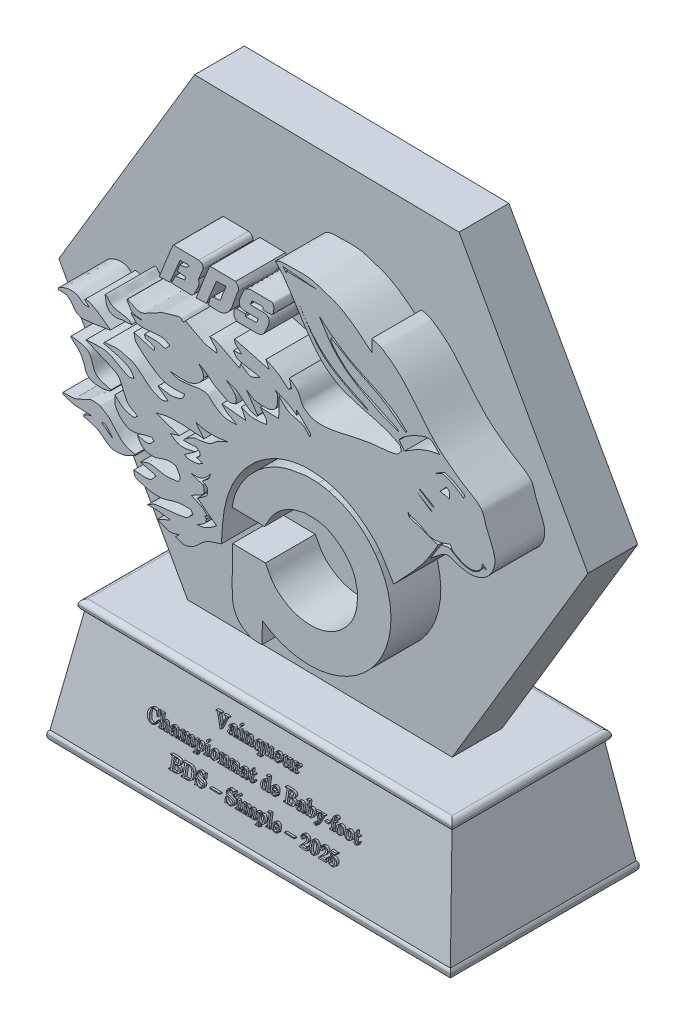
SolidWorks part; units mm, degrees
ref_plane "Plan de face" through (0, 0, 0) normal (0, 0, 1) x (1, 0, 0)
ref_plane "Plan de dessus" through (0, 0, 0) normal (0, 1, 0) x (1, 0, 0)
ref_plane "Plan de droite" through (0, 0, 0) normal (1, 0, 0) x (0, 0, -1)
sketch "Esquisse3" plane through (0, 0, 0) normal (0, 0, 1) x (1, 0, 0)
  line L0 (336.1667, 1024) -> (1680.8333, 1024) construction
  line L1 (1302, 1687) -> (1302, 1736)
  line L2 (1537, 1090) -> (1581, 1159)
  line L3 (1445.599, 1206.4377) -> (1452, 1191)
  line L4 (1452, 1191) -> (1568, 1151)
  line L5 (514, 653) -> (528, 667)
  line L6 (441, 677) -> (494, 701)
  line L7 (584, 764) -> (577, 778)
  line L8 (437, 826) -> (373, 842)
  line L9 (484, 1110) -> (443, 1141)
  line L10 (347, 1280) -> (428, 1256)
  line L11 (428, 1256) -> (430, 1269)
  line L12 (473, 1286) -> (491, 1306)
  line L13 (335, 1341) -> (376, 1337)
  line L14 (376, 1337) -> (378, 1339)
  line L15 (318, 1380) -> (321, 1382)
  line L16 (546, 1414) -> (554, 1424)
  line L17 (771, 1367) -> (775, 1384)
  line L18 (746, 1416) -> (780, 1420)
  line L19 (751, 1459) -> (890, 1422)
  line L20 (890, 1422) -> (877, 1451)
  line L21 (967, 1392) -> (980, 1399)
  line L22 (980, 1399) -> (971, 1433)
  line L23 (945, 1808) -> (1083, 1796)
  line L24 (1083, 1796) -> (959, 1800)
  line L25 (959, 1800) -> (958, 1794)
  line L26 (958, 1794) -> (960, 1791)
  line L27 (960, 1791) -> (945, 1808)
  line L28 (1444, 1481) -> (1437, 1478)
  line L29 (1433, 1410) -> (1411, 1437)
  line L30 (1677, 1373) -> (1670, 1365)
  line L31 (1613, 1334) -> (1576, 1342)
  line L32 (1601, 1369) -> (1576, 1342)
  line L33 (1000, 1318) -> (999, 1338)
  line L34 (999, 1338) -> (1057, 1281)
  line L35 (1057, 1281) -> (1053, 1269)
  line L36 (930, 1348) -> (928, 1270)
  line L37 (928, 1270) -> (855, 1273)
  line L38 (778, 1236) -> (797, 1198)
  line L39 (840, 1234) -> (844, 1240)
  line L40 (844, 1240) -> (799, 1306)
  line L41 (1654, 1326) -> (1658, 1324)
  line L42 (1658, 1324) -> (1654, 1325)
  line L43 (1654, 1326) -> (1654, 1325)
  line L44 (1551, 1277) -> (1494, 1309)
  line L45 (1551, 1277) -> (1549, 1272)
  line L46 (1549, 1272) -> (1493, 1307)
  line L47 (1493, 1307) -> (1494, 1309)
  line L48 (1483, 1293) -> (1544, 1256)
  line L49 (1542, 1254) -> (1544, 1256)
  line L50 (1542, 1254) -> (1483, 1293)
  line L51 (1746, 1175) -> (1763, 1163)
  line L52 (1763, 1163) -> (1760, 1162)
  line L53 (1760, 1162) -> (1750.0098, 1163.665)
  line L55 (1743, 1157) -> (1746, 1175)
  line L56 (598, 970) -> (623, 963)
  line L57 (550, 957) -> (594, 988)
  line L58 (493, 1001) -> (529, 1012)
  line L59 (529, 1012) -> (437, 1044)
  line L60 (595, 1092) -> (628, 1050)
  line L61 (602, 831) -> (679, 773)
  line L62 (638, 777) -> (631, 785)
  line L63 (631, 785) -> (643, 789)
  line L64 (574, 905) -> (625, 888)
  line L65 (232, 1354) -> (231, 1353)
  line L66 (168, 1277) -> (149, 1295)
  line L67 (153, 1299) -> (149, 1295)
  line L68 (255, 1034) -> (253, 1029)
  line L69 (95, 1141) -> (94, 1136)
  line L70 (352, 858) -> (352, 854)
  line L71 (144, 891) -> (144, 887)
  line L72 (144, 891) -> (174, 905)
  line L73 (62, 923) -> (62, 929)
  line L74 (1234, 1501) -> (1241.5869, 1497.8498)
  line L75 (678, 1623) -> (717, 1625)
  line L76 (862.8036, 535.7693) -> (861, 451)
  line L77 (743, 744) -> (875, 742)
  line L78 (871, 867) -> (741, 869)
  line L79 (865, 1617) -> (864, 1628)
  line L80 (821, 1627) -> (864, 1628)
  line L81 (821, 1627) -> (814, 1611)
  line L82 (794, 1568) -> (795, 1559)
  line L83 (795, 1559) -> (839, 1560)
  line L84 (839, 1560) -> (846, 1576)
  line L85 (693, 1564) -> (717, 1625)
  line L86 (700, 1208) -> (797, 1198)
  line L87 (678, 1623) -> (638, 1526)
  line L88 (638, 1526) -> (597, 1525)
  line L89 (498, 1527) -> (513, 1559)
  line L90 (513, 1559) -> (551, 1564)
  line L91 (551, 1564) -> (554, 1576)
  line L92 (554, 1576) -> (521, 1580)
  line L93 (521, 1580) -> (531, 1607)
  line L94 (567, 1620) -> (565, 1624)
  line L95 (565, 1624) -> (532, 1623)
  line L96 (532, 1623) -> (491, 1526)
  line L97 (491, 1526) -> (449, 1525)
  line L98 (624.8796, 1638.9367) -> (605.4226, 1592.9044)
  line L99 (604.6984, 1566.7534) -> (589.7477, 1536.2154)
  line L100 (573.9653, 1525) -> (498, 1527)
  line L101 (264.0246, 866.4916) -> (217, 902)
  arc A0 (607, 1661) -> (624.8796, 1638.9367) centre (606.6207, 1642.4164) cw
  arc A1 (605.4226, 1592.9044) -> (604.6984, 1566.7534) centre (576.3678, 1580.6235) cw
  arc A2 (589.7477, 1536.2154) -> (573.9653, 1525) centre (571.5353, 1545.1319) cw
  arc A3 (862.8036, 535.7693) -> (1316.5669, 993.1753) centre (1052.5129, 801.3486) ccw
  arc A4 (1129.8066, 1118.4411) -> (1086.8314, 1125.9164) centre (1052.5129, 801.3486) ccw
  spline S0 degree 3 poles (915, 1811) (920.6667, 1813.6667) (925.9164, 1817.5129) (932, 1819) (941.1183, 1821.2289) (950.6154, 1822.1997) (960, 1822) (1000.4122, 1821.1402) (1042.9169, 1827.5488) (1081, 1814) (1113.09, 1802.5833) (1146.9207, 1794.9796) (1177, 1779) (1222.6884, 1754.728) (1262.8151, 1720.7801) (1302, 1687) knots 0 0 0 0 1 1 1 2 2 2 3 3 3 4 4 4 5 5 5 5
  spline S1 degree 3 poles (1302, 1736) (1317, 1730.3333) (1333.5756, 1727.7691) (1347, 1719) (1375.3732, 1700.4659) (1402.4901, 1679.4098) (1426, 1655) (1472.4253, 1606.7976) (1509.2053, 1549.8439) (1556, 1502) (1583.8463, 1473.5293) (1617.0572, 1450.7835) (1649, 1427) (1678.4402, 1405.0798) (1714.1626, 1391.0701) (1740, 1365) (1752.6359, 1352.2503) (1753.5167, 1331.7388) (1760, 1315) (1771.8506, 1284.4039) (1788.3447, 1255.1289) (1795, 1223) (1798.2706, 1207.2107) (1795.1053, 1189.924) (1789, 1175) (1782.6895, 1159.5742) (1772.3333, 1145) (1759, 1135) (1744.6396, 1124.2297) (1726.7988, 1117.3288) (1709, 1115) (1690.0565, 1112.5214) (1670.8107, 1117.6598) (1652, 1121) (1635.0445, 1124.0108) (1618.6273, 1138.4821) (1602, 1134) (1576.7377, 1127.1902) (1558.6667, 1104.6667) (1537, 1090) knots 0 0 0 0 1 1 1 2 2 2 3 3 3 4 4 4 5 5 5 6 6 6 7 7 7 8 8 8 9 9 9 10 10 10 11 11 11 12 12 12 13 13 13 13
  spline S2 degree 3 poles (1581, 1159) (1592.9734, 1159.921) (1605.2835, 1164.5242) (1617, 1162.6354) knots 0 0 0 0 0.921032 0.921032 0.921032 0.921032
  spline S3 degree 3 poles (1626.6587, 1159.5467) (1622.8097, 1165.1023) (1620.6123, 1172.2204) (1617, 1178) knots 2.277549 2.277549 2.277549 2.277549 3 3 3 3
  spline S4 degree 3 poles (1617, 1178) (1603, 1173.6667) (1589.4463, 1167.4664) (1575, 1165) (1561.8527, 1162.7553) (1547.9107, 1160.6528) (1535, 1164) (1519.9865, 1167.8924) (1508.1253, 1179.5944) (1494, 1186) (1479.3968, 1192.6224) (1461.6455, 1193.1408) (1449, 1203) (1447.7012, 1204.0126) (1446.5813, 1205.1696) (1445.599, 1206.4377) knots 0 0 0 0 1 1 1 2 2 2 3 3 3 4 4 4 4.153424 4.153424 4.153424 4.153424
  spline S5 degree 3 poles (1568, 1151) (1562.6667, 1142) (1557.7044, 1132.7695) (1552, 1124) (1535.3644, 1098.4259) (1520.3192, 1071.6124) (1501, 1048) (1466.1847, 1005.448) (1427, 966.6667) (1390, 926) knots 0 0 0 0 1 1 1 2 2 2 3 3 3 3
  spline S6 degree 3 poles (1390, 926) (1370, 957.3333) (1353.6926, 991.3567) (1330, 1020) (1308.6483, 1045.8133) (1283.3166, 1068.6086) (1256, 1088) (1228.8829, 1107.2498) (1199.2278, 1123.5669) (1168, 1135) (1137.6118, 1146.1257) (1105.2971, 1152.9709) (1073, 1155) (1040.9523, 1157.0135) (1008.2798, 1154.2583) (977, 1147) (947.2739, 1140.1022) (918.485, 1128.1581) (892, 1113) (864.9769, 1097.534) (839.9344, 1078.0981) (818, 1056) (794.8916, 1032.7191) (774.5075, 1006.3461) (758, 978) (741.238, 949.2167) (728.0873, 918.0447) (719, 886) (703.7834, 832.3415) (700.9314, 775.6973) (698, 720) knots 0 0 0 0 1 1 1 2 2 2 3 3 3 4 4 4 5 5 5 6 6 6 7 7 7 8 8 8 9 9 9 10 10 10 10
  spline S7 degree 3 poles (698, 720) (678, 712.6667) (656.4567, 708.6361) (638, 698) (616.6203, 685.6795) (602.0285, 663.1191) (580, 652) (548.5317, 636.116) (537.3019, 642.1258) (514, 653) knots 0 0 0 0 1 1 1 2 2 2 3 3 3 3
  spline S8 degree 3 poles (528, 667) (525.4489, 666.4898) (497.27, 654.9179) (484, 660) (469.6066, 665.5124) (455.3333, 671.3333) (441, 677) knots 0 0 0 0 1 1 1 2 2 2 2
  spline S9 degree 3 poles (494, 701) (477, 703.3333) (460.1099, 706.6982) (443, 708) (429.3727, 709.0369) (415.6667, 708) (402, 708) knots 0 0 0 0 1 1 1 2 2 2 2
  spline S10 degree 3 poles (402, 708) (412, 713.3333) (420.9098, 721.6652) (432, 724) (472.1351, 732.4495) (514.3355, 729.562) (554, 740) (566.3846, 743.2591) (574, 756) (584, 764) knots 0 0 0 0 1 1 1 2 2 2 3 3 3 3
  spline S11 degree 3 poles (577, 778) (560, 777.6667) (542.804, 779.5957) (526, 777) (501.5513, 773.2234) (478.6767, 760.7501) (454, 759) (430.9039, 757.362) (407.166, 760.3084) (385, 767) (348.0895, 778.1428) (350.2029, 779.9856) (346, 801) knots 0 0 0 0 1 1 1 2 2 2 3 3 3 4 4 4 4
  spline S12 degree 3 poles (346, 801) (367.6667, 801) (390.1074, 795.2603) (411, 801) (422.5936, 804.185) (428.3333, 817.6667) (437, 826) knots 0 0 0 0 1 1 1 2 2 2 2
  spline S13 degree 3 poles (373, 842) (385, 846.3333) (396.25, 854.5364) (409, 855) (435.1955, 855.9526) (460.8999, 842.5721) (487, 845) (500.0501, 846.214) (513, 848.3333) (526, 850) knots 0 0 0 0 1 1 1 2 2 2 3 3 3 3
  spline S14 degree 3 poles (526, 850) (528, 856.3333) (533.3025, 862.4874) (532, 869) (529.7195, 880.4027) (521.3333, 889.6667) (516, 900) knots 0 0 0 0 1 1 1 2 2 2 2
  spline S15 degree 3 poles (516, 900) (505.3333, 901) (494.6103, 904.4832) (484, 903) (463.1813, 900.0899) (443.9834, 888.259) (423, 887) (409.6035, 886.1962) (395.1111, 889.4731) (384, 897) (373.1244, 904.3673) (368.6667, 918.3333) (361, 929) knots 0 0 0 0 1 1 1 2 2 2 3 3 3 4 4 4 4
  spline S16 degree 3 poles (361, 929) (376, 927) (391.1443, 920.1176) (406, 923) (415.5122, 924.8457) (420.6667, 935.6667) (428, 942) knots 0 0 0 0 1 1 1 2 2 2 2
  spline S17 degree 3 poles (428, 942) (424, 944.6667) (420.7819, 950.4947) (416, 950) (390.5019, 947.3623) (366.6332, 933.2229) (341, 933) (326.6401, 932.8751) (312.2458, 940.0695) (301, 949) (288.6786, 958.7846) (279.0102, 972.4593) (273, 987) (268.2733, 998.4355) (271, 1011.6667) (270, 1024) knots 0 0 0 0 1 1 1 2 2 2 3 3 3 4 4 4 5 5 5 5
  spline S18 degree 3 poles (270, 1024) (283.6667, 1013.6667) (294.8981, 998.8552) (311, 993) (347.6119, 979.6866) (348.3963, 982.3963) (362, 996) knots 0 0 0 0 1 1 1 2 2 2 2
  spline S19 degree 3 poles (362, 996) (349.3333, 1004) (334.0691, 1008.9069) (324, 1020) (313.6798, 1031.3697) (310.3408, 1047.5133) (303, 1061) (296.0028, 1073.8554) (292.6952, 1090.1997) (281, 1099) (257.6507, 1116.5698) (228.5806, 1124.8608) (202, 1137) (186.2331, 1144.2006) (170, 1150.3333) (154, 1157) knots 0 0 0 0 1 1 1 2 2 2 3 3 3 4 4 4 5 5 5 5
  spline S20 degree 3 poles (154, 1157) (155.3333, 1157.3333) (156.6257, 1157.9838) (158, 1158) (184.9981, 1158.3176) (212.8154, 1164.5853) (239, 1158) (269.9392, 1150.2189) (294.8755, 1126.5021) (325, 1116) (332.348, 1113.4383) (340.3333, 1118.6667) (348, 1120) knots 0 0 0 0 1 1 1 2 2 2 3 3 3 4 4 4 4
  spline S21 degree 3 poles (348, 1120) (341.6667, 1128.6667) (337.8909, 1139.9855) (329, 1146) (298.4419, 1166.6716) (259.637, 1171.4544) (224, 1181) knots 0 0 0 0 1 1 1 2 2 2 2
  spline S22 degree 3 poles (224, 1181) (226, 1182.6667) (227.4051, 1185.7896) (230, 1186) (253.9215, 1187.9396) (279.1881, 1193.4577) (302, 1186) (318.0306, 1180.7592) (335.4753, 1178.5719) (350, 1170) (376.6403, 1154.2779) (396.4202, 1128.0088) (424, 1114) (459.6438, 1095.8952) (463.5958, 1099.7979) (484, 1110) knots 0 0 0 0 1 1 1 2 2 2 3 3 3 4 4 4 5 5 5 5
  spline S23 degree 3 poles (443, 1141) (448.6949, 1142.8983) (443.1637, 1141.6511) (450, 1141) (469.6483, 1139.1287) (489.5876, 1132.4345) (509, 1136) (542.4065, 1142.1359) (543.3635, 1148.1815) (551, 1166) knots 0 0 0 0 1 1 1 2 2 2 3 3 3 3
  spline S24 degree 3 poles (551, 1166) (526.3333, 1166.3333) (501.1599, 1162.0146) (477, 1167) (458.1643, 1170.8867) (440.8598, 1181.1209) (425, 1192) (400.2227, 1208.996) (375.9299, 1227.515) (356, 1250) (349.0749, 1257.813) (350, 1270) (347, 1280) knots 0 0 0 0 1 1 1 2 2 2 3 3 3 4 4 4 4
  spline S25 degree 3 poles (430, 1269) (388.8184, 1289.0628) (394.9727, 1274.0957) (389, 1295) knots 0 0 0 0 1 1 1 1
  spline S26 degree 3 poles (389, 1295) (407, 1294.6667) (425.0994, 1295.9179) (443, 1294) (453.2906, 1292.8974) (463, 1288.6667) (473, 1286) knots 0 0 0 0 1 1 1 2 2 2 2
  spline S27 degree 3 poles (491, 1306) (482, 1310.3333) (473.9581, 1318.2159) (464, 1319) (430.7546, 1321.6178) (396.8737, 1310.3936) (364, 1316) (351.4189, 1318.1456) (344.6667, 1332.6667) (335, 1341) knots 0 0 0 0 1 1 1 2 2 2 3 3 3 3
  spline S28 degree 3 poles (378, 1339) (365.6667, 1341.6667) (351.4183, 1339.8809) (341, 1347) (329.9297, 1354.5647) (325.6667, 1369) (318, 1380) knots 0 0 0 0 1 1 1 2 2 2 2
  spline S29 degree 3 poles (321, 1382) (337.6667, 1375.6667) (353.1715, 1362.8181) (371, 1363) (388.3324, 1363.1769) (403.2308, 1375.8044) (419, 1383) (437.5803, 1391.4784) (454.2051, 1404.9727) (474, 1410) (535.009, 1425.4944) (528.4316, 1431.5684) (546, 1414) knots 0 0 0 0 1 1 1 2 2 2 3 3 3 4 4 4 4
  spline S30 degree 3 poles (554, 1424) (579.3333, 1410.6667) (603.3907, 1394.5593) (630, 1384) (645.7983, 1377.7308) (663.3333, 1377.3333) (680, 1374) knots 0 0 0 0 1 1 1 2 2 2 2
  spline S31 degree 3 poles (680, 1374) (679.3333, 1378) (680.2674, 1382.638) (678, 1386) (670.338, 1397.3609) (660, 1406.6667) (651, 1417) knots 0 0 0 0 1 1 1 2 2 2 2
  spline S32 degree 3 poles (651, 1417) (660, 1416) (669.6412, 1417.4828) (678, 1414) (710.0621, 1400.6408) (740, 1382.6667) (771, 1367) knots 0 0 0 0 1 1 1 2 2 2 2
  spline S33 degree 3 poles (775, 1384) (791.3079, 1376.2006) (808.3586, 1355.94) (825, 1363) (834.7522, 1367.1373) (844.3333, 1371.6667) (854, 1376) knots 0 0 0 0 1 1 1 2 2 2 2
  spline S34 degree 3 poles (854, 1376) (846, 1378) (838.054, 1380.2299) (830, 1382) (807.7162, 1386.8975) (784.1489, 1387.4397) (763, 1396) (754.8896, 1399.2828) (751.6667, 1409.3333) (746, 1416) knots 0 0 0 0 1 1 1 2 2 2 3 3 3 3
  spline S35 degree 3 poles (780, 1420) (749.6731, 1451.41) (753.337, 1435.6296) (751, 1459) knots 0 0 0 0 1 1 1 1
  spline S36 degree 3 poles (877, 1451) (893.6667, 1442.3333) (911.2896, 1435.2991) (927, 1425) (941.4558, 1415.5234) (953.6667, 1403) (967, 1392) knots 0 0 0 0 1 1 1 2 2 2 2
  spline S37 degree 3 poles (971, 1433) (982, 1424) (995.2325, 1417.1862) (1004, 1406) (1014.9466, 1392.0336) (1015.9477, 1371.0219) (1029, 1359) (1042.717, 1346.3659) (1061.5274, 1338.5577) (1080, 1336) (1108.8188, 1332.0097) (1138.5521, 1336.904) (1167, 1343) (1206.3139, 1351.4244) (1245.3733, 1361.1971) (1285, 1368) (1323.1007, 1374.5409) (1362.6291, 1373.1077) (1400, 1383) (1409.5699, 1385.5332) (1414, 1397) (1421, 1404) knots 0 0 0 0 1 1 1 2 2 2 3 3 3 4 4 4 5 5 5 6 6 6 7 7 7 7
  spline S38 degree 3 poles (1421, 1404) (1418.3333, 1410) (1418.5514, 1418.4939) (1413, 1422) (1392.0534, 1435.2294) (1368.4815, 1444.1007) (1345, 1452) (1296.0045, 1468.4823) (1244.0544, 1475.9476) (1196, 1495) (1167.7816, 1506.1879) (1141.5168, 1522.8061) (1118, 1542) (1095.6955, 1560.2044) (1076.9818, 1582.7512) (1060, 1606) (1020.8468, 1659.6027) (988.3318, 1717.8068) (950, 1772) (939.9132, 1786.2607) (926.6667, 1798) (915, 1811) knots 0 0 0 0 1 1 1 2 2 2 3 3 3 4 4 4 5 5 5 6 6 6 7 7 7 7
  spline S39 degree 3 poles (1234, 1501) (1233.3071, 1501.2746) (1232.6555, 1501.6452) (1232, 1502) (1204.3218, 1516.9788) (1175.736, 1530.3978) (1149, 1547) (1118.5402, 1565.9145) (1091.9951, 1591.6844) (1070, 1620) (1033.5835, 1666.8811) (1004.352, 1718.9828) (974, 1770) knots 5 5 5 5 6 6 6 7 7 7 8 8 8 9 9 9 9
  spline S40 degree 3 poles (974, 1770) (1009.2632, 1712.8836) (1040.7926, 1651.7205) (1088, 1604) (1103.129, 1588.7065) (1119.6469, 1574.7141) (1137, 1562) (1153.4175, 1549.9713) (1171.1465, 1539.7712) (1189, 1530) (1220.5161, 1512.7513) (1254.8005, 1500.4619) (1285, 1481) (1298.4541, 1472.3296) (1262.1817, 1489.0571) (1241.5869, 1497.8498) knots 0 0 0 0 1 1 1 2 2 2 3 3 3 4 4 4 4.876532 4.876532 4.876532 4.876532
  spline S41 degree 3 poles (1091, 1708) (1133.0564, 1673.7942) (1174.7177, 1637.6494) (1223, 1613) (1284.8912, 1581.4029) (1352.3155, 1557.8776) (1407, 1515) (1420.1811, 1504.6649) (1431.6667, 1492.3333) (1444, 1481) knots 0 0 0 0 1 1 1 2 2 2 3 3 3 3
  spline S42 degree 3 poles (1437, 1478) (1402.4117, 1505.2291) (1367.5024, 1532.6613) (1329, 1554) (1294.7083, 1573.005) (1258.5431, 1588.4558) (1224, 1607) (1195.1856, 1622.4688) (1167.3333, 1639.6667) (1139, 1656) knots 0 0 0 0 1 1 1 2 2 2 3 3 3 3
  spline S43 degree 3 poles (1139, 1656) (1139.3333, 1650.6667) (1136.7754, 1644.2611) (1140, 1640) (1156.078, 1618.7541) (1175.1654, 1599.7898) (1195, 1582) (1207.6652, 1570.6405) (1221.9981, 1561.0243) (1237, 1553) (1279.4612, 1530.2882) (1323.6737, 1511.0145) (1367, 1490) (1406.2609, 1470.9573) (1395.2349, 1482.5182) (1409, 1466) knots 0 0 0 0 1 1 1 2 2 2 3 3 3 4 4 4 5 5 5 5
  spline S44 degree 3 poles (1409, 1466) (1382.5166, 1475.5954) (1354.8689, 1482.7719) (1330, 1496) (1264.0429, 1531.0836) (1201.8033, 1560.9883) (1152, 1618) (1128.157, 1645.2939) (1110.3276, 1677.3424) (1091, 1708) knots 0 0 0 0 1 1 1 2 2 2 3 3 3 3
  spline S45 degree 3 poles (1411, 1437) (1422.7965, 1460.5929) (1479.2149, 1489.3274) (1503, 1497) (1509.6241, 1499.1368) (1516.0477, 1502.6689) (1523, 1503) (1528.3377, 1503.2542) (1533.6929, 1502.6244) (1539, 1502) (1546.2224, 1501.1503) (1568.8037, 1474.1963) (1574, 1469) knots 0 0 0 0 1 1 1 2 2 2 3 3 3 4 4 4 4
  spline S46 degree 3 poles (1574, 1469) (1515.6013, 1461.3828) (1480.7028, 1441.8019) (1433, 1410) knots 0 0 0 0 1 1 1 1
  spline S47 degree 3 poles (1556, 1394) (1558.3701, 1396.3701) (1590.3583, 1416) (1594, 1416) (1607.1855, 1416) (1667.2767, 1387.5849) (1677, 1373) knots 0 0 0 0 1 1 1 2 2 2 2
  spline S48 degree 3 poles (1670, 1365) (1657.2666, 1377.7334) (1604.6796, 1406.1748) (1589, 1407) (1577.874, 1407.5856) (1564.0025, 1397.8273) (1556, 1394) knots 0 0 0 0 1 1 1 2 2 2 2
  spline S49 degree 3 poles (1601, 1369) (1604.5506, 1366.1595) (1613.803, 1362.3203) (1614, 1357) (1614.284, 1349.3313) (1613.3333, 1341.6667) (1613, 1334) knots 0 0 0 0 1 1 1 2 2 2 2
  spline S50 degree 3 poles (914, 1363) (932, 1355.3333) (950.665, 1349.0706) (968, 1340) (979.4691, 1333.9987) (989.3333, 1325.3333) (1000, 1318) knots 0 0 0 0 1 1 1 2 2 2 2
  spline S51 degree 3 poles (1053, 1269) (1043.6667, 1278.3333) (1036.6084, 1290.7178) (1025, 1297) (1007.4766, 1306.4832) (985.5551, 1305.5757) (968, 1315) (953.219, 1322.9351) (942.6667, 1337) (930, 1348) knots 0 0 0 0 1 1 1 2 2 2 3 3 3 3
  spline S52 degree 3 poles (855, 1273) (882.3131, 1233.6692) (882.4018, 1251.411) (878, 1225) knots 0 0 0 0 1 1 1 1
  spline S53 degree 3 poles (878, 1225) (860.3333, 1223.6667) (842.6107, 1219.0628) (825, 1221) (808.6534, 1222.7981) (793.6667, 1231) (778, 1236) knots 0 0 0 0 1 1 1 2 2 2 2
  spline S54 degree 3 poles (700, 1208) (706.3333, 1201.6667) (711.7033, 1194.1943) (719, 1189) (731.5298, 1180.0804) (745.6667, 1173.6667) (759, 1166) knots 0 0 0 0 1 1 1 2 2 2 2
  spline S55 degree 3 poles (759, 1166) (757, 1165.3333) (755.1067, 1163.922) (753, 1164) (736.9555, 1164.5942) (720.3884, 1163.4201) (705, 1168) (691.6848, 1171.9629) (680.5843, 1181.3316) (669, 1189) (656.8812, 1197.0223) (648.4052, 1213.0732) (634, 1215) (592.68, 1220.5269) (547.8534, 1195.8903) (509, 1211) (503.981, 1212.9518) (499, 1215) (494, 1217) knots 0 0 0 0 1 1 1 2 2 2 3 3 3 4 4 4 5 5 5 6 6 6 6
  spline S56 degree 3 poles (494, 1217) (517.3333, 1216.3333) (540.9428, 1211.3594) (564, 1215) (579.9136, 1217.5127) (595.0147, 1225.4639) (608, 1235) (617.0274, 1241.6295) (621.3333, 1253) (628, 1262) knots 0 0 0 0 1 1 1 2 2 2 3 3 3 3
  spline S57 degree 3 poles (628, 1262) (625.6667, 1269.3333) (624.5116, 1277.1523) (621, 1284) (617.7448, 1290.3476) (612.3333, 1295.3333) (608, 1301) knots 0 0 0 0 1 1 1 2 2 2 2
  spline S58 degree 3 poles (608, 1301) (617.3333, 1295.6667) (627.138, 1291.0844) (636, 1285) (649.5212, 1275.7168) (660.3578, 1262.3895) (675, 1255) (734.878, 1224.7812) (723.0011, 1223.8575) (757, 1236) knots 0 0 0 0 1 1 1 2 2 2 3 3 3 3
  spline S59 degree 3 poles (757, 1236) (756.6667, 1244.3333) (759.5511, 1253.4538) (756, 1261) (748.0708, 1277.8495) (730.7925, 1288.6881) (716, 1300) knots 0 0 0 0 1 1 1 2 2 2 2
  spline S60 degree 3 poles (716, 1300) (730, 1294.6667) (745.1306, 1291.6696) (758, 1284) (778.4448, 1271.8157) (794.6796, 1253.3905) (815, 1241) (822.3886, 1236.4947) (831.6667, 1236.3333) (840, 1234) knots 0 0 0 0 1 1 1 2 2 2 3 3 3 3
  spline S61 degree 3 poles (799, 1306) (810.3333, 1299.3333) (820.288, 1289.3606) (833, 1286) (850.1072, 1281.4774) (868.3163, 1283.6316) (886, 1283) (887.0534, 1282.9624) (888.0572, 1283.5286) (889, 1284) (896.7345, 1287.8672) (906.3175, 1289.4818) (912, 1296) (918.3862, 1303.3254) (922.4031, 1313.3001) (923, 1323) (924.841, 1352.9155) (924.4477, 1352.5523) (914, 1363) knots 0 0 0 0 1 1 1 2 2 2 3 3 3 4 4 4 5 5 5 6 6 6 6
  spline S62 degree 3 poles (595, 1092) (609.6667, 1088.6667) (624.0211, 1083.3617) (639, 1082) (675.9728, 1078.6388) (692.3078, 1083.4907) (725, 1088) knots 0 0 0 0 1 1 1 2 2 2 2
  spline S63 degree 3 poles (725, 1088) (711.5274, 1081.2637) (696.9722, 1076.6557) (684, 1069) (673.3204, 1062.6973) (664.9736, 1052.7756) (654, 1047) (645.6935, 1042.6282) (636.1763, 1040.9764) (627, 1039) (602.8772, 1033.8043) (599.6204, 1038.6814) (587, 1032) (576.3252, 1026.3486) (565.0499, 1021.6999) (555, 1015) (550.8769, 1012.2513) (548.3333, 1007.6667) (545, 1004) knots 0 0 0 0 1 1 1 2 2 2 3 3 3 4 4 4 5 5 5 6 6 6 6
  spline S64 degree 3 poles (545, 1004) (600.4214, 1002.0889) (592.1008, 1015.5116) (613, 992) knots 0 0 0 0 1 1 1 1
  spline S65 degree 3 poles (613, 992) (612.3333, 988.6667) (612.915, 984.8086) (611, 982) (607.6779, 977.1275) (602.3333, 974) (598, 970) knots 0 0 0 0 1 1 1 2 2 2 2
  spline S66 degree 3 poles (623, 963) (617.6667, 959.6667) (612.9666, 954.9889) (607, 953) (598.6813, 950.2271) (589.7671, 948.8346) (581, 949) (558.8759, 949.4174) (560.1362, 949.3979) (550, 957) knots 0 0 0 0 1 1 1 2 2 2 3 3 3 3
  spline S67 degree 3 poles (594, 988) (578, 985) (562.2776, 979.201) (546, 979) (520.046, 978.6796) (511.1814, 987.869) (493, 1001) knots 0 0 0 0 1 1 1 2 2 2 2
  spline S68 degree 3 poles (437, 1044) (438.3333, 1044.6667) (439.5424, 1045.6877) (441, 1046) (458.2591, 1049.6984) (475.4011, 1054.6462) (493, 1056) (519.5902, 1058.0454) (546.4778, 1057.7918) (573, 1055) (591.3078, 1053.0729) (609.6667, 1051.6667) (628, 1050) knots 0 0 0 0 1 1 1 2 2 2 3 3 3 4 4 4 4
  spline S69 degree 3 poles (655, 941) (652.6667, 934.6667) (652.1823, 927.2976) (648, 922) (641.8381, 914.1949) (632.3071, 909.745) (625, 903) (623.5718, 901.6817) (623, 899.6667) (622, 898) knots 0 0 0 0 1 1 1 2 2 2 3 3 3 3
  spline S70 degree 3 poles (622, 898) (627.7349, 895.1326) (635.2169, 894.1768) (639, 889) (644.2386, 881.8315) (644.3408, 863.1311) (637, 856) (626.7162, 846.01) (613.1955, 839.9564) (602, 831) knots 0 0 0 0 1 1 1 2 2 2 3 3 3 3
  spline S71 degree 3 poles (679, 773) (653.2815, 754.2956) (635.6045, 739) (603, 739) knots 0 0 0 0 1 1 1 1
  spline S72 degree 3 poles (603, 739) (613, 746) (624.7304, 751.0215) (633, 760) (637.0016, 764.3446) (636.3333, 771.3333) (638, 777) knots 0 0 0 0 1 1 1 2 2 2 2
  spline S73 degree 3 poles (643, 789) (635.3333, 795.6667) (628.6155, 803.6153) (620, 809) (606.7117, 817.3052) (591.5494, 822.1802) (577, 828) knots 0 0 0 0 1 1 1 2 2 2 2
  spline S74 degree 3 poles (577, 828) (616.4664, 852.9685) (638.0843, 848.747) (625, 888) knots 0 0 0 0 1 1 1 1
  spline S75 degree 3 poles (574, 905) (587.3333, 905.6667) (601.3163, 902.8352) (614, 907) (630.8684, 912.5389) (642.4457, 928.4457) (655, 941) knots 0 0 0 0 1 1 1 2 2 2 2
  spline S76 degree 3 poles (232, 1354) (242.4415, 1351.9117) (248.1212, 1335.3194) (258, 1330) (283.5429, 1316.2461) (317.1934, 1324.8066) (339, 1303) knots 0 0 0 0 1 1 1 2 2 2 2
  spline S77 degree 3 poles (339, 1303) (338.3333, 1302.3333) (337.9399, 1301.0742) (337, 1301) (325.0326, 1300.0552) (312.9871, 1300.648) (301, 1300) (296.7122, 1299.7682) (287.0907, 1296) (283, 1296) (239.2897, 1296) (236.3377, 1315.6359) (231, 1353) knots 0 0 0 0 1 1 1 2 2 2 3 3 3 4 4 4 4
  spline S78 degree 3 poles (42, 1277) (43, 1279.3333) (42.9398, 1282.5167) (45, 1284) (51.6537, 1288.7907) (59.2562, 1292.3065) (67, 1295) (74.7182, 1297.6846) (82.8298, 1299.8398) (91, 1300) (100.0965, 1300.1784) (109.5318, 1299.3268) (118, 1296) (128.5895, 1291.8398) (136.3646, 1282.0414) (147, 1278) (153.5509, 1275.5107) (161, 1277.3333) (168, 1277) knots 0 0 0 0 1 1 1 2 2 2 3 3 3 4 4 4 5 5 5 6 6 6 6
  spline S79 degree 3 poles (153, 1299) (192.7282, 1291.9891) (220.1759, 1262.8827) (253, 1241) knots 0 0 0 0 1 1 1 1
  spline S80 degree 3 poles (253, 1241) (252.3333, 1240.6667) (251.7352, 1240.1225) (251, 1240) (210.5395, 1233.2566) (176.8812, 1226.7192) (137, 1224) (136.2564, 1223.9493) (135.673, 1224.6795) (135, 1225) (128.6728, 1228.0129) (121.209, 1229.3119) (116, 1234) (104.2292, 1244.5937) (97.4114, 1260.1646) (85, 1270) (73.6184, 1279.0194) (56.5056, 1276.3093) (42, 1277) knots 0 0 0 0 1 1 1 2 2 2 3 3 3 4 4 4 5 5 5 6 6 6 6
  spline S81 degree 3 poles (95, 1141) (114.8476, 1138.9108) (147.1123, 1136.4433) (163, 1122) (187.4478, 1099.7747) (173.8492, 1057.8926) (219, 1044) (219.3388, 1043.8958) (245.2794, 1035.9441) (255, 1034) knots 0 0 0 0 1 1 1 2 2 2 3 3 3 3
  spline S82 degree 3 poles (253, 1029) (243.9623, 1025.9874) (234.6235, 1022.6637) (225, 1022) (203.027, 1020.4846) (168.7372, 1020.6485) (156, 1044) (151.1278, 1052.9324) (149.628, 1063.5673) (146, 1073) (142.3376, 1082.5223) (136.6973, 1092.4541) (131, 1101) (121.2159, 1115.6762) (106.0916, 1123.9084) (94, 1136) knots 0 0 0 0 1 1 1 2 2 2 3 3 3 4 4 4 5 5 5 5
  spline S83 degree 3 poles (62, 929) (77.3333, 929.3333) (92.6763, 929.3615) (108, 930) (108.7447, 930.031) (109.3133, 930.7101) (110, 931) (124.3148, 937.044) (138.77, 942.7588) (153, 949) (161.8999, 952.9034) (170.2844, 959.7741) (180, 960) (190.0472, 960.2337) (200.0277, 958.2465) (210, 957) (210.7396, 956.9075) (211.3659, 956.3917) (212, 956) (222.7019, 949.39) (234.3976, 944.1251) (244, 936) (256.2407, 925.6425) (265.9722, 912.6404) (277, 901) (283.9723, 893.6403) (289.9517, 885.1646) (298, 879) (305.8143, 873.0146) (314.8261, 868.5676) (324, 865) (332.9664, 861.5131) (342.6667, 860.3333) (352, 858) knots 0 0 0 0 1 1 1 2 2 2 3 3 3 4 4 4 5 5 5 6 6 6 7 7 7 8 8 8 9 9 9 10 10 10 11 11 11 11
  spline S84 degree 3 poles (352, 854) (338.6667, 847.6667) (326.0036, 839.6679) (312, 835) (301.7579, 831.586) (290.7946, 830.1799) (280, 830) (270.5732, 829.8429) (260.4327, 829.7836) (252, 834) (233.8035, 843.0982) (219.813, 859.1721) (202, 869) (184.2757, 878.7789) (163.6925, 882.3113) (144, 887) knots 0 0 0 0 1 1 1 2 2 2 3 3 3 4 4 4 5 5 5 5
  spline S85 degree 3 poles (174, 905) (144.9735, 907.7319) (114.3398, 903.8741) (87, 914) (78.6945, 917.0761) (70.3333, 920) (62, 923) knots 0 0 0 0 1 1 1 2 2 2 2
  spline S86 degree 3 poles (217, 902) (237.2594, 912.1297) (250.3229, 878.0008) (264.0246, 866.4916) knots 0 0 0 0 0.954263 0.954263 0.954263 0.954263
  spline S87 degree 3 poles (741, 869) (745.6667, 887.3333) (747.7541, 906.5247) (755, 924) (764.8836, 947.837) (777.0331, 970.9791) (792, 992) (806.9169, 1012.9507) (824.8476, 1031.8352) (844, 1049) (860.3907, 1063.6898) (878.7758, 1076.2821) (898, 1087) (916.6558, 1097.401) (936.5111, 1105.9645) (957, 1112) (979.7651, 1118.706) (1003.646, 1120.7794) (1027, 1125) (1031.3144, 1125.7797) (1035.6196, 1127.1844) (1040, 1127) (1063.1964, 1126.0233) (1077.3953, 1125.9069) (1086.8314, 1125.9164) knots 0 0 0 0 1 1 1 2 2 2 3 3 3 4 4 4 5 5 5 6 6 6 7 7 7 7.312652 7.312652 7.312652 7.312652
  spline S88 degree 3 poles (1129.8066, 1118.4411) (1149.3282, 1112.2707) (1169.4776, 1107.6732) (1188, 1099) (1210.21, 1088.6001) (1231.5798, 1075.9766) (1251, 1061) (1276.9315, 1041.002) (1298.6831, 1018.304) (1316.5669, 993.1753) knots 8.076053 8.076053 8.076053 8.076053 9 9 9 10 10 10 10.407544 10.407544 10.407544 10.407544
  spline S89 degree 3 poles (861, 451) (860.7904, 451.0102) (822.8237, 449.1685) (811, 456) (798.6701, 463.124) (785.1535, 469.0158) (775, 479) (764.7166, 489.112) (756.2735, 501.5765) (751, 515) (745.0476, 530.1515) (742.5683, 546.7311) (742, 563) (739.8935, 623.2975) (742.6667, 683.6667) (743, 744) knots 0 0 0 0 1 1 1 2 2 2 3 3 3 4 4 4 5 5 5 5
  spline S90 degree 3 poles (875, 742) (886.3333, 722.6667) (894.6188, 701.1873) (909, 684) (922.3654, 668.0268) (939.2502, 654.8959) (957, 644) (973.3018, 633.993) (991.3781, 626.3721) (1010, 622) (1030.1849, 617.2609) (1051.3145, 615.5856) (1072, 617) (1090.7946, 618.2851) (1109.6347, 622.6968) (1127, 630) (1145.7608, 637.8901) (1163.6526, 648.6329) (1179, 662) (1195.0596, 675.9874) (1208.9898, 692.77) (1220, 711) (1229.601, 726.8968) (1236.1194, 744.8388) (1240, 763) (1244.5408, 784.251) (1243.7239, 806.3068) (1245, 828) (1245.0619, 829.0523) (1244.2849, 829.9851) (1244, 831) (1238.9512, 848.9864) (1237.0946, 868.1632) (1229, 885) (1220.1849, 903.3353) (1207.9538, 920.1953) (1194, 935) (1180.3243, 949.5096) (1164.2355, 961.9753) (1147, 972) (1131.2153, 981.1809) (1113.9175, 988.4777) (1096, 992) (1074.3909, 996.248) (1052.0135, 994.3619) (1030, 995) (1028.9463, 995.0305) (1028.0082, 994.3076) (1027, 994) (1008.3412, 988.3075) (988.4483, 985.7242) (971, 977) (952.6309, 967.8155) (935.7836, 955.2556) (921, 941) (899.5706, 920.3359) (885.381, 893.0655) (871, 867) knots 0 0 0 0 1 1 1 2 2 2 3 3 3 4 4 4 5 5 5 6 6 6 7 7 7 8 8 8 9 9 9 10 10 10 11 11 11 12 12 12 13 13 13 14 14 14 15 15 15 16 16 16 17 17 17 18 18 18 19 19 19 19
  spline S91 degree 3 poles (846, 1576) (825.6667, 1576.3333) (805.3255, 1576.3443) (785, 1577) (784.5288, 1577.0152) (784.4216, 1577.7892) (784, 1578) (781.0636, 1579.4682) (777.3214, 1579.6786) (775, 1582) (763.606, 1593.394) (773.1825, 1614.365) (779, 1626) (782.4673, 1632.9346) (785.5327, 1640.0654) (789, 1647) (794.1673, 1657.3346) (809.3479, 1662.8816) (820, 1663) (846.0005, 1663.2889) (872.0062, 1662.6581) (898, 1662) (913.4911, 1661.6078) (908.2556, 1631.6817) (905, 1623) (904.1724, 1620.7931) (902.3379, 1618.2997) (900, 1618) (888.4233, 1616.5158) (876.6667, 1617.3333) (865, 1617) knots 0 0 0 0 1 1 1 2 2 2 3 3 3 4 4 4 5 5 5 6 6 6 7 7 7 8 8 8 9 9 9 10 10 10 10
  spline S92 degree 3 poles (814, 1611) (834.3961, 1607.6007) (855.3353, 1609.7251) (876, 1609) (876.4711, 1608.9835) (876.5784, 1608.2108) (877, 1608) (900.3349, 1596.3325) (886.7947, 1573.5894) (878, 1556) (871.5364, 1543.0728) (872.5797, 1541.8957) (866, 1534) (861.0143, 1528.0171) (851.4293, 1524.2346) (844, 1524) (816.3471, 1523.1268) (788.6647, 1523.6707) (761, 1524) (760.5286, 1524.0056) (760.4093, 1524.7661) (760, 1525) (745.7347, 1533.1516) (744.2607, 1553.1129) (755, 1566) (756.4315, 1567.7178) (758.7669, 1568.8855) (761, 1569) (771.9906, 1569.5636) (783, 1568.3333) (794, 1568) knots 0 0 0 0 1 1 1 2 2 2 3 3 3 4 4 4 5 5 5 6 6 6 7 7 7 8 8 8 9 9 9 10 10 10 10
  spline S93 degree 3 poles (597, 1525) (614.6667, 1570) (631.5443, 1615.3178) (650, 1660) (650.6363, 1661.5404) (652.3334, 1662.9841) (654, 1663) (687.6717, 1663.3207) (721.3333, 1661.6667) (755, 1661) knots 0 0 0 0 1 1 1 2 2 2 3 3 3 3
  spline S94 degree 3 poles (755, 1661) (758.3333, 1656.6667) (763.712, 1653.3132) (765, 1648) (769.3984, 1629.8564) (765.2762, 1633.7036) (762, 1626) (745.1615, 1586.4069) (740.6004, 1525.4277) (688, 1523) (673.999, 1522.3538) (660, 1524.3333) (646, 1525) knots 0 0 0 0 1 1 1 2 2 2 3 3 3 4 4 4 4
  spline S95 degree 3 poles (646, 1525) (649.1605, 1534.4815) (649.9589, 1557.3414) (665, 1561) (674.1208, 1563.2186) (683.6667, 1563) (693, 1564) knots 0 0 0 0 1 1 1 2 2 2 2
  spline S96 degree 3 poles (449, 1525) (467, 1570) (483.6751, 1615.5528) (503, 1660) (503.8916, 1662.0506) (506.764, 1662.9785) (509, 1663) (541.672, 1663.3142) (574.3333, 1661.6667) (607, 1661) knots 0 0 0 0 1 1 1 2 2 2 3 3 3 3
  spline S97 degree 3 poles (531, 1607) (548.3042, 1610.708) (556.4301, 1605.9067) (567, 1620) knots 0 0 0 0 1 1 1 1
  spline S98 degree 3 poles (1626.6587, 1159.5467) (1661.3206, 1136.2747) (1712.7818, 1114.6388) (1743, 1157) knots 0 0 0 0 1 1 1 1
  spline S99 degree 3 poles (1617, 1162.6354) (1656.216, 1134.436) (1715.0222, 1104.1743) (1750.0098, 1163.665) knots 0 0 0 0 1 1 1 1
  point P209 (862.8036, 535.7693)
  point P210 (1316.5669, 993.1753)
extrude "Boss.-Extru.1" add sketch "Esquisse3" along normal blind 200
sketch "Esquisse4" plane through (0, 0, 0) normal (0, 0, -1) x (-1, 0, 0)
  line L0 (-875, 742) -> (-743, 744) construction
  line L1 (-390.38, 2097.2194) -> (-1452.38, 2081.1285)
  line L2 (-1452.38, 2081.1285) -> (-1969.4449, 1153.364)
  line L3 (-1969.4449, 1153.364) -> (-1424.5097, 241.6905)
  line L4 (-1424.5097, 241.6905) -> (-362.5097, 257.7814)
  line L5 (-362.5097, 257.7814) -> (154.5551, 1185.5459)
  line L6 (154.5551, 1185.5459) -> (-390.38, 2097.2194)
  circle A0 centre (-907.4449, 1169.455) radius 919.8245 construction
  dimension "D1" = 1062
extrude "Boss.-Extru.2" add sketch "Esquisse4" along normal blind 200 separate body
sketch "Esquisse5" plane through (3.9881, 263.2136, 0) normal (-0.0151, -0.9999, 0) x (0.9999, -0.0151, 0)
  line L1 (158.5628, 200) -> (1620.6847, 200)
  line L2 (158.5628, 200) -> (158.5628, -400)
  line L3 (158.5628, -400) -> (1620.6847, -400)
  line L4 (1620.6847, 200) -> (1620.6847, -400)
  line L7 (1420.6847, 0) -> (358.5628, 0) construction
  line L8 (1420.6847, -200) -> (358.5628, -200) construction
  line L9 (1420.6847, -200) -> (1420.6847, 0) construction
  line L10 (358.5628, -200) -> (358.5628, 0) construction
  dimension "D1" = 200
  dimension "D2" = 200
  dimension "D3" = 200
  dimension "D4" = 200
extrude "Boss.-Extru.3" add sketch "Esquisse5" along normal blind 500 draft 9 draft outward yes
sketch "Esquisse11" plane through (3.9881, 263.2136, 0) normal (0.0151, 0.9999, 0) x (0.9999, -0.0151, 0)
  line L0 (158.5628, 400) -> (1620.6847, 400) construction
  line L1 (138.5628, 420) -> (1640.6847, 420)
  line L2 (138.5628, 420) -> (138.5628, -220)
  line L3 (138.5628, -220) -> (1640.6847, -220)
  line L4 (1640.6847, 420) -> (1640.6847, -220)
  line L5 (1620.6847, 400) -> (1620.6847, -200) construction
  line L6 (1620.6847, -200) -> (158.5628, -200) construction
  line L7 (158.5628, -200) -> (158.5628, 400) construction
  dimension "D1" = 20
  dimension "D2" = 20
  dimension "D3" = 20
  dimension "D4" = 20
extrude "Boss.-Extru.7" add sketch "Esquisse11" against normal blind 40
fillet "Congé1" radius 20 8 edges at (141.929, 221.119, -100) (142.535, 261.1144, -100) (892.9037, 209.7406, -420) (893.5097, 249.736, -420) (1644.4845, 238.3576, -100) (1643.8785, 198.3622, -100) (892.9037, 209.7406, 220) (893.5097, 249.736, 220)
sketch "Esquisse15" plane through (-3.5868, -236.729, 0) normal (-0.0151, -0.9999, 0) x (0.9999, -0.0151, 0)
  line L4 (79.3706, 279.1922) -> (79.3706, -479.1922)
  line L5 (79.3706, -479.1922) -> (1699.8769, -479.1922)
  line L6 (1699.8769, -479.1922) -> (1699.8769, 279.1922)
  line L7 (1699.8769, 279.1922) -> (79.3706, 279.1922)
  line L8 (79.3706, 279.1922) -> (79.3706, -479.1922)
  line L9 (79.3706, -479.1922) -> (1699.8769, -479.1922)
  line L10 (1699.8769, -479.1922) -> (1699.8769, 279.1922)
  line L11 (1699.8769, 279.1922) -> (79.3706, 279.1922)
  dimension "D1" = 0
extrude "Boss.-Extru.8" add sketch "Esquisse15" against normal blind 40
fillet "Congé5" radius 20 8 edges at (75.7747, -237.9315, -100) (76.3806, -197.9361, -100) (885.9348, -250.2066, 279.1922) (886.5408, -210.2112, 279.1922) (1696.095, -262.4818, -100) (885.9348, -250.2066, -479.1922) (886.5408, -210.2112, -479.1922) (1696.701, -222.4864, -100)
sketch "Esquisse17" plane through (0.5657, 37.3394, 235.7791) normal (0.0024, 0.1564, 0.9877) x (1, -0.0004, -0.0023)
  line L0 (885.9776, -250.3032) -> (892.3405, 174.8845) construction
  line L1 (1689.8054, -262.3325) -> (82.1498, -238.2739) construction
  line L2 (155.0267, 185.9184) -> (1629.6543, 163.8507) construction
  line L3 (118.5883, -26.1778) -> (1659.7298, -49.2409) construction
  line L4 (82.1498, -238.2739) -> (155.0267, 185.9184) construction
  line L5 (1689.8054, -262.3325) -> (1629.6543, 163.8507) construction
  line L6 (118.5883, -26.1778) -> (155.0267, 185.9184) construction
  line L7 (136.8075, 79.8703) -> (1644.692, 57.3049) construction
  text T0 "Vainqueur  \r\nChampionnat de Baby-foot  \r\nBDS – Simple – 2025" font "Century Schoolbook" height 50
extrude "Boss.-Extru.10" add sketch "Esquisse17" along normal blind 10 separate body
